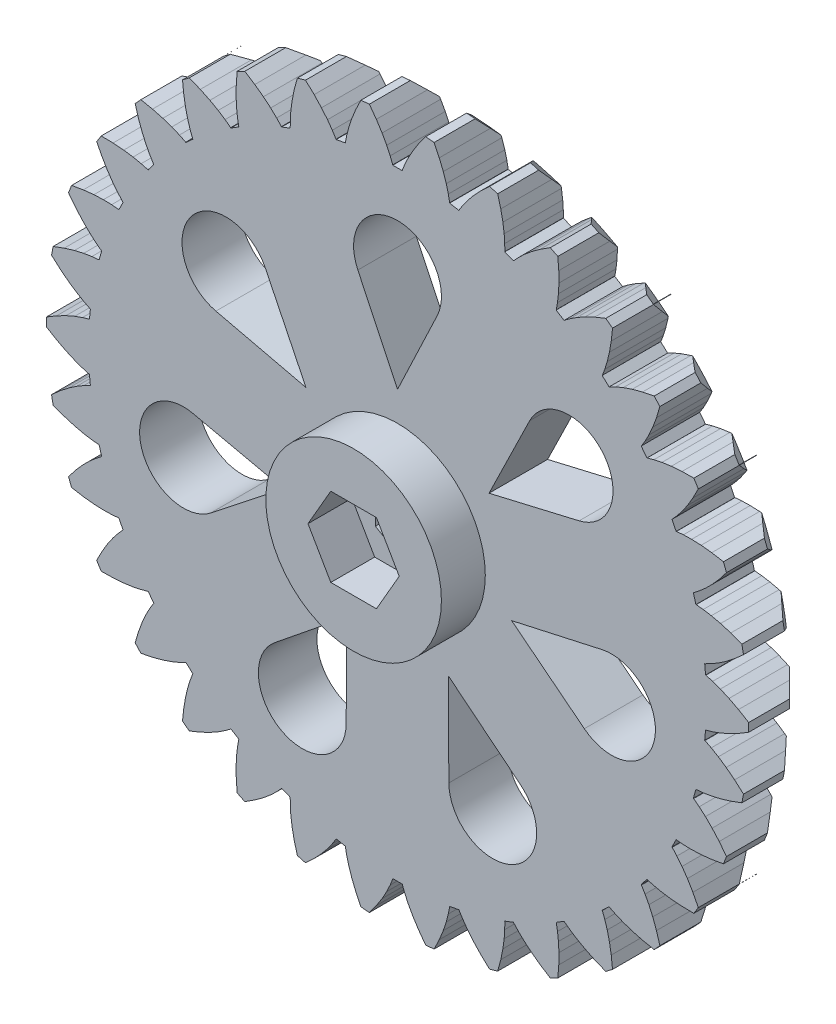
SolidWorks part; units mm, degrees
material "Custom Plastic"
ref_plane "Front Plane" through (0, 0, 0) normal (0, 0, 1) x (1, 0, 0)
ref_plane "Top Plane" through (0, 0, 0) normal (0, 1, 0) x (1, 0, 0)
ref_plane "Right Plane" through (0, 0, 0) normal (1, 0, 0) x (0, 0, -1)
sketch "Model" plane through (0, 0, 0) normal (0, 0, 1) x (1, 0, 0)
  line L0 (-23.998, -0.289) -> (-23.998, 0.289)
  line L1 (-23.998, 0.289) -> (-23.301, 0.707)
  line L2 (-23.301, 0.707) -> (-22.653, 1.042)
  line L3 (-22.653, 1.042) -> (-22.061, 1.301)
  line L4 (-22.061, 1.301) -> (-21.531, 1.492)
  line L5 (-21.531, 1.492) -> (-21.071, 1.627)
  line L6 (-21.071, 1.627) -> (-21.05, 1.625)
  line L7 (-21.05, 1.625) -> (-20.99, 2.27)
  line L8 (-20.99, 2.27) -> (-21.011, 2.272)
  line L9 (-21.011, 2.272) -> (-21.439, 2.49)
  line L10 (-21.439, 2.49) -> (-21.924, 2.775)
  line L11 (-21.924, 2.775) -> (-22.459, 3.138)
  line L12 (-22.459, 3.138) -> (-23.034, 3.587)
  line L13 (-23.034, 3.587) -> (-23.642, 4.126)
  line L14 (-23.642, 4.126) -> (-23.536, 4.694)
  line L15 (-23.536, 4.694) -> (-22.774, 4.977)
  line L16 (-22.774, 4.977) -> (-22.076, 5.187)
  line L17 (-22.076, 5.187) -> (-21.446, 5.333)
  line L18 (-21.446, 5.333) -> (-20.89, 5.423)
  line L19 (-20.89, 5.423) -> (-20.413, 5.471)
  line L20 (-20.413, 5.471) -> (-20.393, 5.466)
  line L21 (-20.393, 5.466) -> (-20.216, 6.089)
  line L22 (-20.216, 6.089) -> (-20.236, 6.095)
  line L23 (-20.236, 6.095) -> (-20.616, 6.387)
  line L24 (-20.616, 6.387) -> (-21.041, 6.756)
  line L25 (-21.041, 6.756) -> (-21.5, 7.212)
  line L26 (-21.5, 7.212) -> (-21.983, 7.758)
  line L27 (-21.983, 7.758) -> (-22.482, 8.4)
  line L28 (-22.482, 8.4) -> (-22.273, 8.939)
  line L29 (-22.273, 8.939) -> (-21.472, 9.077)
  line L30 (-21.472, 9.077) -> (-20.747, 9.155)
  line L31 (-20.747, 9.155) -> (-20.101, 9.182)
  line L32 (-20.101, 9.182) -> (-19.538, 9.169)
  line L33 (-19.538, 9.169) -> (-19.06, 9.129)
  line L34 (-19.06, 9.129) -> (-19.042, 9.12)
  line L35 (-19.042, 9.12) -> (-18.753, 9.7)
  line L36 (-18.753, 9.7) -> (-18.771, 9.709)
  line L37 (-18.771, 9.709) -> (-19.091, 10.066)
  line L38 (-19.091, 10.066) -> (-19.442, 10.507)
  line L39 (-19.442, 10.507) -> (-19.809, 11.039)
  line L40 (-19.809, 11.039) -> (-20.183, 11.665)
  line L41 (-20.183, 11.665) -> (-20.556, 12.388)
  line L42 (-20.556, 12.388) -> (-20.251, 12.879)
  line L43 (-20.251, 12.879) -> (-19.439, 12.867)
  line L44 (-19.439, 12.867) -> (-18.711, 12.811)
  line L45 (-18.711, 12.811) -> (-18.072, 12.72)
  line L46 (-18.072, 12.72) -> (-17.521, 12.603)
  line L47 (-17.521, 12.603) -> (-17.058, 12.476)
  line L48 (-17.058, 12.476) -> (-17.042, 12.464)
  line L49 (-17.042, 12.464) -> (-16.652, 12.98)
  line L50 (-16.652, 12.98) -> (-16.668, 12.993)
  line L51 (-16.668, 12.993) -> (-16.917, 13.403)
  line L52 (-16.917, 13.403) -> (-17.18, 13.901)
  line L53 (-17.18, 13.901) -> (-17.443, 14.491)
  line L54 (-17.443, 14.491) -> (-17.696, 15.175)
  line L55 (-17.696, 15.175) -> (-17.929, 15.954)
  line L56 (-17.929, 15.954) -> (-17.54, 16.381)
  line L57 (-17.54, 16.381) -> (-16.743, 16.22)
  line L58 (-16.743, 16.22) -> (-16.039, 16.031)
  line L59 (-16.039, 16.031) -> (-15.427, 15.824)
  line L60 (-15.427, 15.824) -> (-14.906, 15.608)
  line L61 (-14.906, 15.608) -> (-14.476, 15.398)
  line L62 (-14.476, 15.398) -> (-14.462, 15.383)
  line L63 (-14.462, 15.383) -> (-13.983, 15.82)
  line L64 (-13.983, 15.82) -> (-13.996, 15.835)
  line L65 (-13.996, 15.835) -> (-14.166, 16.283)
  line L66 (-14.166, 16.283) -> (-14.333, 16.821)
  line L67 (-14.333, 16.821) -> (-14.483, 17.45)
  line L68 (-14.483, 17.45) -> (-14.606, 18.169)
  line L69 (-14.606, 18.169) -> (-14.693, 18.977)
  line L70 (-14.693, 18.977) -> (-14.231, 19.325)
  line L71 (-14.231, 19.325) -> (-13.478, 19.021)
  line L72 (-13.478, 19.021) -> (-12.82, 18.705)
  line L73 (-12.82, 18.705) -> (-12.257, 18.389)
  line L74 (-12.257, 18.389) -> (-11.785, 18.081)
  line L75 (-11.785, 18.081) -> (-11.4, 17.796)
  line L76 (-11.4, 17.796) -> (-11.389, 17.779)
  line L77 (-11.389, 17.779) -> (-10.838, 18.119)
  line L78 (-10.838, 18.119) -> (-10.849, 18.137)
  line L79 (-10.849, 18.137) -> (-10.933, 18.609)
  line L80 (-10.933, 18.609) -> (-10.998, 19.168)
  line L81 (-10.998, 19.168) -> (-11.03, 19.814)
  line L82 (-11.03, 19.814) -> (-11.019, 20.543)
  line L83 (-11.019, 20.543) -> (-10.956, 21.353)
  line L84 (-10.956, 21.353) -> (-10.438, 21.611)
  line L85 (-10.438, 21.611) -> (-9.753, 21.173)
  line L86 (-9.753, 21.173) -> (-9.165, 20.743)
  line L87 (-9.165, 20.743) -> (-8.669, 20.328)
  line L88 (-8.669, 20.328) -> (-8.262, 19.939)
  line L89 (-8.262, 19.939) -> (-7.936, 19.587)
  line L90 (-7.936, 19.587) -> (-7.928, 19.568)
  line L91 (-7.928, 19.568) -> (-7.324, 19.802)
  line L92 (-7.324, 19.802) -> (-7.331, 19.821)
  line L93 (-7.331, 19.821) -> (-7.327, 20.301)
  line L94 (-7.327, 20.301) -> (-7.289, 20.863)
  line L95 (-7.289, 20.863) -> (-7.202, 21.503)
  line L96 (-7.202, 21.503) -> (-7.057, 22.218)
  line L97 (-7.057, 22.218) -> (-6.845, 23.003)
  line L98 (-6.845, 23.003) -> (-6.289, 23.161)
  line L99 (-6.289, 23.161) -> (-5.697, 22.605)
  line L100 (-5.697, 22.605) -> (-5.197, 22.073)
  line L101 (-5.197, 22.073) -> (-4.786, 21.575)
  line L102 (-4.786, 21.575) -> (-4.457, 21.117)
  line L103 (-4.457, 21.117) -> (-4.201, 20.712)
  line L104 (-4.201, 20.712) -> (-4.197, 20.692)
  line L105 (-4.197, 20.692) -> (-3.56, 20.81)
  line L106 (-3.56, 20.81) -> (-3.564, 20.831)
  line L107 (-3.564, 20.831) -> (-3.472, 21.301)
  line L108 (-3.472, 21.301) -> (-3.331, 21.847)
  line L109 (-3.331, 21.847) -> (-3.128, 22.46)
  line L110 (-3.128, 22.46) -> (-2.854, 23.136)
  line L111 (-2.854, 23.136) -> (-2.502, 23.869)
  line L112 (-2.502, 23.869) -> (-1.926, 23.922)
  line L113 (-1.926, 23.922) -> (-1.446, 23.267)
  line L114 (-1.446, 23.267) -> (-1.053, 22.653)
  line L115 (-1.053, 22.653) -> (-0.74, 22.087)
  line L116 (-0.74, 22.087) -> (-0.501, 21.577)
  line L117 (-0.501, 21.577) -> (-0.324, 21.131)
  line L118 (-0.324, 21.131) -> (-0.324, 21.111)
  line L119 (-0.324, 21.111) -> (0.324, 21.11)
  line L120 (0.324, 21.11) -> (0.324, 21.131)
  line L121 (0.324, 21.131) -> (0.501, 21.577)
  line L122 (0.501, 21.577) -> (0.74, 22.087)
  line L123 (0.74, 22.087) -> (1.053, 22.653)
  line L124 (1.053, 22.653) -> (1.446, 23.267)
  line L125 (1.446, 23.267) -> (1.926, 23.922)
  line L126 (1.926, 23.922) -> (2.502, 23.869)
  line L127 (2.502, 23.869) -> (2.854, 23.136)
  line L128 (2.854, 23.136) -> (3.128, 22.46)
  line L129 (3.128, 22.46) -> (3.331, 21.847)
  line L130 (3.331, 21.847) -> (3.472, 21.301)
  line L131 (3.472, 21.301) -> (3.564, 20.831)
  line L132 (3.564, 20.831) -> (3.56, 20.81)
  line L133 (3.56, 20.81) -> (4.197, 20.692)
  line L134 (4.197, 20.692) -> (4.201, 20.712)
  line L135 (4.201, 20.712) -> (4.457, 21.117)
  line L136 (4.457, 21.117) -> (4.786, 21.575)
  line L137 (4.786, 21.575) -> (5.197, 22.073)
  line L138 (5.197, 22.073) -> (5.697, 22.605)
  line L139 (5.697, 22.605) -> (6.289, 23.161)
  line L140 (6.289, 23.161) -> (6.845, 23.003)
  line L141 (6.845, 23.003) -> (7.057, 22.218)
  line L142 (7.057, 22.218) -> (7.202, 21.503)
  line L143 (7.202, 21.503) -> (7.289, 20.863)
  line L144 (7.289, 20.863) -> (7.327, 20.301)
  line L145 (7.327, 20.301) -> (7.331, 19.821)
  line L146 (7.331, 19.821) -> (7.324, 19.802)
  line L147 (7.324, 19.802) -> (7.928, 19.568)
  line L148 (7.928, 19.568) -> (7.936, 19.587)
  line L149 (7.936, 19.587) -> (8.262, 19.939)
  line L150 (8.262, 19.939) -> (8.669, 20.328)
  line L151 (8.669, 20.328) -> (9.165, 20.743)
  line L152 (9.165, 20.743) -> (9.753, 21.173)
  line L153 (9.753, 21.173) -> (10.438, 21.611)
  line L154 (10.438, 21.611) -> (10.956, 21.353)
  line L155 (10.956, 21.353) -> (11.019, 20.543)
  line L156 (11.019, 20.543) -> (11.03, 19.814)
  line L157 (11.03, 19.814) -> (10.998, 19.168)
  line L158 (10.998, 19.168) -> (10.933, 18.609)
  line L159 (10.933, 18.609) -> (10.849, 18.137)
  line L160 (10.849, 18.137) -> (10.838, 18.119)
  line L161 (10.838, 18.119) -> (11.389, 17.778)
  line L162 (11.389, 17.778) -> (11.4, 17.796)
  line L163 (11.4, 17.796) -> (11.785, 18.081)
  line L164 (11.785, 18.081) -> (12.257, 18.389)
  line L165 (12.257, 18.389) -> (12.82, 18.705)
  line L166 (12.82, 18.705) -> (13.478, 19.021)
  line L167 (13.478, 19.021) -> (14.231, 19.325)
  line L168 (14.231, 19.325) -> (14.693, 18.977)
  line L169 (14.693, 18.977) -> (14.606, 18.169)
  line L170 (14.606, 18.169) -> (14.483, 17.45)
  line L171 (14.483, 17.45) -> (14.333, 16.821)
  line L172 (14.333, 16.821) -> (14.166, 16.283)
  line L173 (14.166, 16.283) -> (13.996, 15.835)
  line L174 (13.996, 15.835) -> (13.983, 15.82)
  line L175 (13.983, 15.82) -> (14.462, 15.383)
  line L176 (14.462, 15.383) -> (14.476, 15.398)
  line L177 (14.476, 15.398) -> (14.906, 15.608)
  line L178 (14.906, 15.608) -> (15.427, 15.824)
  line L179 (15.427, 15.824) -> (16.039, 16.031)
  line L180 (16.039, 16.031) -> (16.743, 16.22)
  line L181 (16.743, 16.22) -> (17.54, 16.381)
  line L182 (17.54, 16.381) -> (17.929, 15.954)
  line L183 (17.929, 15.954) -> (17.696, 15.175)
  line L184 (17.696, 15.175) -> (17.443, 14.491)
  line L185 (17.443, 14.491) -> (17.18, 13.901)
  line L186 (17.18, 13.901) -> (16.917, 13.403)
  line L187 (16.917, 13.403) -> (16.668, 12.993)
  line L188 (16.668, 12.993) -> (16.652, 12.981)
  line L189 (16.652, 12.981) -> (17.042, 12.464)
  line L190 (17.042, 12.464) -> (17.058, 12.476)
  line L191 (17.058, 12.476) -> (17.521, 12.603)
  line L192 (17.521, 12.603) -> (18.072, 12.72)
  line L193 (18.072, 12.72) -> (18.711, 12.811)
  line L194 (18.711, 12.811) -> (19.439, 12.867)
  line L195 (19.439, 12.867) -> (20.251, 12.879)
  line L196 (20.251, 12.879) -> (20.556, 12.388)
  line L197 (20.556, 12.388) -> (20.183, 11.665)
  line L198 (20.183, 11.665) -> (19.809, 11.039)
  line L199 (19.809, 11.039) -> (19.442, 10.507)
  line L200 (19.442, 10.507) -> (19.091, 10.066)
  line L201 (19.091, 10.066) -> (18.771, 9.709)
  line L202 (18.771, 9.709) -> (18.753, 9.7)
  line L203 (18.753, 9.7) -> (19.042, 9.12)
  line L204 (19.042, 9.12) -> (19.06, 9.129)
  line L205 (19.06, 9.129) -> (19.538, 9.169)
  line L206 (19.538, 9.169) -> (20.101, 9.182)
  line L207 (20.101, 9.182) -> (20.747, 9.155)
  line L208 (20.747, 9.155) -> (21.472, 9.077)
  line L209 (21.472, 9.077) -> (22.273, 8.939)
  line L210 (22.273, 8.939) -> (22.482, 8.4)
  line L211 (22.482, 8.4) -> (21.983, 7.758)
  line L212 (21.983, 7.758) -> (21.5, 7.212)
  line L213 (21.5, 7.212) -> (21.041, 6.756)
  line L214 (21.041, 6.756) -> (20.616, 6.387)
  line L215 (20.616, 6.387) -> (20.236, 6.095)
  line L216 (20.236, 6.095) -> (20.216, 6.089)
  line L217 (20.216, 6.089) -> (20.393, 5.466)
  line L218 (20.393, 5.466) -> (20.413, 5.471)
  line L219 (20.413, 5.471) -> (20.89, 5.423)
  line L220 (20.89, 5.423) -> (21.446, 5.333)
  line L221 (21.446, 5.333) -> (22.076, 5.187)
  line L222 (22.076, 5.187) -> (22.774, 4.977)
  line L223 (22.774, 4.977) -> (23.536, 4.694)
  line L224 (23.536, 4.694) -> (23.642, 4.126)
  line L225 (23.642, 4.126) -> (23.034, 3.587)
  line L226 (23.034, 3.587) -> (22.459, 3.138)
  line L227 (22.459, 3.138) -> (21.924, 2.775)
  line L228 (21.924, 2.775) -> (21.439, 2.49)
  line L229 (21.439, 2.49) -> (21.011, 2.272)
  line L230 (21.011, 2.272) -> (20.99, 2.27)
  line L231 (20.99, 2.27) -> (21.051, 1.625)
  line L232 (21.051, 1.625) -> (21.071, 1.627)
  line L233 (21.071, 1.627) -> (21.531, 1.492)
  line L234 (21.531, 1.492) -> (22.061, 1.301)
  line L235 (22.061, 1.301) -> (22.653, 1.042)
  line L236 (22.653, 1.042) -> (23.301, 0.707)
  line L237 (23.301, 0.707) -> (23.998, 0.289)
  line L238 (23.998, 0.289) -> (23.998, -0.289)
  line L239 (23.998, -0.289) -> (23.301, -0.707)
  line L240 (23.301, -0.707) -> (22.653, -1.042)
  line L241 (22.653, -1.042) -> (22.061, -1.301)
  line L242 (22.061, -1.301) -> (21.531, -1.492)
  line L243 (21.531, -1.492) -> (21.071, -1.627)
  line L244 (21.071, -1.627) -> (21.05, -1.625)
  line L245 (21.05, -1.625) -> (20.99, -2.27)
  line L246 (20.99, -2.27) -> (21.011, -2.272)
  line L247 (21.011, -2.272) -> (21.439, -2.49)
  line L248 (21.439, -2.49) -> (21.924, -2.775)
  line L249 (21.924, -2.775) -> (22.459, -3.138)
  line L250 (22.459, -3.138) -> (23.034, -3.587)
  line L251 (23.034, -3.587) -> (23.642, -4.126)
  line L252 (23.642, -4.126) -> (23.536, -4.694)
  line L253 (23.536, -4.694) -> (22.774, -4.977)
  line L254 (22.774, -4.977) -> (22.076, -5.187)
  line L255 (22.076, -5.187) -> (21.446, -5.333)
  line L256 (21.446, -5.333) -> (20.89, -5.423)
  line L257 (20.89, -5.423) -> (20.413, -5.471)
  line L258 (20.413, -5.471) -> (20.393, -5.466)
  line L259 (20.393, -5.466) -> (20.216, -6.089)
  line L260 (20.216, -6.089) -> (20.236, -6.095)
  line L261 (20.236, -6.095) -> (20.616, -6.387)
  line L262 (20.616, -6.387) -> (21.041, -6.756)
  line L263 (21.041, -6.756) -> (21.5, -7.212)
  line L264 (21.5, -7.212) -> (21.983, -7.758)
  line L265 (21.983, -7.758) -> (22.482, -8.4)
  line L266 (22.482, -8.4) -> (22.273, -8.939)
  line L267 (22.273, -8.939) -> (21.472, -9.077)
  line L268 (21.472, -9.077) -> (20.747, -9.155)
  line L269 (20.747, -9.155) -> (20.101, -9.182)
  line L270 (20.101, -9.182) -> (19.538, -9.169)
  line L271 (19.538, -9.169) -> (19.06, -9.129)
  line L272 (19.06, -9.129) -> (19.042, -9.12)
  line L273 (19.042, -9.12) -> (18.753, -9.7)
  line L274 (18.753, -9.7) -> (18.771, -9.709)
  line L275 (18.771, -9.709) -> (19.091, -10.066)
  line L276 (19.091, -10.066) -> (19.442, -10.507)
  line L277 (19.442, -10.507) -> (19.809, -11.039)
  line L278 (19.809, -11.039) -> (20.183, -11.665)
  line L279 (20.183, -11.665) -> (20.556, -12.388)
  line L280 (20.556, -12.388) -> (20.251, -12.879)
  line L281 (20.251, -12.879) -> (19.439, -12.867)
  line L282 (19.439, -12.867) -> (18.711, -12.811)
  line L283 (18.711, -12.811) -> (18.072, -12.72)
  line L284 (18.072, -12.72) -> (17.521, -12.603)
  line L285 (17.521, -12.603) -> (17.058, -12.476)
  line L286 (17.058, -12.476) -> (17.042, -12.464)
  line L287 (17.042, -12.464) -> (16.652, -12.98)
  line L288 (16.652, -12.98) -> (16.668, -12.993)
  line L289 (16.668, -12.993) -> (16.917, -13.403)
  line L290 (16.917, -13.403) -> (17.18, -13.901)
  line L291 (17.18, -13.901) -> (17.443, -14.491)
  line L292 (17.443, -14.491) -> (17.696, -15.175)
  line L293 (17.696, -15.175) -> (17.929, -15.954)
  line L294 (17.929, -15.954) -> (17.54, -16.381)
  line L295 (17.54, -16.381) -> (16.743, -16.22)
  line L296 (16.743, -16.22) -> (16.039, -16.031)
  line L297 (16.039, -16.031) -> (15.427, -15.824)
  line L298 (15.427, -15.824) -> (14.906, -15.608)
  line L299 (14.906, -15.608) -> (14.476, -15.398)
  line L300 (14.476, -15.398) -> (14.462, -15.383)
  line L301 (14.462, -15.383) -> (13.983, -15.82)
  line L302 (13.983, -15.82) -> (13.996, -15.835)
  line L303 (13.996, -15.835) -> (14.166, -16.283)
  line L304 (14.166, -16.283) -> (14.333, -16.821)
  line L305 (14.333, -16.821) -> (14.483, -17.45)
  line L306 (14.483, -17.45) -> (14.606, -18.169)
  line L307 (14.606, -18.169) -> (14.693, -18.977)
  line L308 (14.693, -18.977) -> (14.231, -19.325)
  line L309 (14.231, -19.325) -> (13.478, -19.021)
  line L310 (13.478, -19.021) -> (12.82, -18.705)
  line L311 (12.82, -18.705) -> (12.257, -18.389)
  line L312 (12.257, -18.389) -> (11.785, -18.081)
  line L313 (11.785, -18.081) -> (11.4, -17.796)
  line L314 (11.4, -17.796) -> (11.389, -17.779)
  line L315 (11.389, -17.779) -> (10.838, -18.119)
  line L316 (10.838, -18.119) -> (10.849, -18.137)
  line L317 (10.849, -18.137) -> (10.933, -18.609)
  line L318 (10.933, -18.609) -> (10.998, -19.168)
  line L319 (10.998, -19.168) -> (11.03, -19.814)
  line L320 (11.03, -19.814) -> (11.019, -20.543)
  line L321 (11.019, -20.543) -> (10.956, -21.353)
  line L322 (10.956, -21.353) -> (10.438, -21.611)
  line L323 (10.438, -21.611) -> (9.753, -21.173)
  line L324 (9.753, -21.173) -> (9.165, -20.743)
  line L325 (9.165, -20.743) -> (8.669, -20.328)
  line L326 (8.669, -20.328) -> (8.262, -19.939)
  line L327 (8.262, -19.939) -> (7.936, -19.587)
  line L328 (7.936, -19.587) -> (7.928, -19.568)
  line L329 (7.928, -19.568) -> (7.324, -19.802)
  line L330 (7.324, -19.802) -> (7.331, -19.821)
  line L331 (7.331, -19.821) -> (7.327, -20.301)
  line L332 (7.327, -20.301) -> (7.289, -20.863)
  line L333 (7.289, -20.863) -> (7.202, -21.503)
  line L334 (7.202, -21.503) -> (7.057, -22.218)
  line L335 (7.057, -22.218) -> (6.845, -23.003)
  line L336 (6.845, -23.003) -> (6.289, -23.161)
  line L337 (6.289, -23.161) -> (5.697, -22.605)
  line L338 (5.697, -22.605) -> (5.197, -22.073)
  line L339 (5.197, -22.073) -> (4.786, -21.575)
  line L340 (4.786, -21.575) -> (4.457, -21.117)
  line L341 (4.457, -21.117) -> (4.201, -20.712)
  line L342 (4.201, -20.712) -> (4.197, -20.692)
  line L343 (4.197, -20.692) -> (3.56, -20.81)
  line L344 (3.56, -20.81) -> (3.564, -20.831)
  line L345 (3.564, -20.831) -> (3.472, -21.301)
  line L346 (3.472, -21.301) -> (3.331, -21.847)
  line L347 (3.331, -21.847) -> (3.128, -22.46)
  line L348 (3.128, -22.46) -> (2.854, -23.136)
  line L349 (2.854, -23.136) -> (2.502, -23.869)
  line L350 (2.502, -23.869) -> (1.926, -23.922)
  line L351 (1.926, -23.922) -> (1.446, -23.267)
  line L352 (1.446, -23.267) -> (1.053, -22.653)
  line L353 (1.053, -22.653) -> (0.74, -22.087)
  line L354 (0.74, -22.087) -> (0.501, -21.577)
  line L355 (0.501, -21.577) -> (0.324, -21.131)
  line L356 (0.324, -21.131) -> (0.324, -21.111)
  line L357 (0.324, -21.111) -> (-0.324, -21.11)
  line L358 (-0.324, -21.11) -> (-0.324, -21.131)
  line L359 (-0.324, -21.131) -> (-0.501, -21.577)
  line L360 (-0.501, -21.577) -> (-0.74, -22.087)
  line L361 (-0.74, -22.087) -> (-1.053, -22.653)
  line L362 (-1.053, -22.653) -> (-1.446, -23.267)
  line L363 (-1.446, -23.267) -> (-1.926, -23.922)
  line L364 (-1.926, -23.922) -> (-2.502, -23.869)
  line L365 (-2.502, -23.869) -> (-2.854, -23.136)
  line L366 (-2.854, -23.136) -> (-3.128, -22.46)
  line L367 (-3.128, -22.46) -> (-3.331, -21.847)
  line L368 (-3.331, -21.847) -> (-3.472, -21.301)
  line L369 (-3.472, -21.301) -> (-3.564, -20.831)
  line L370 (-3.564, -20.831) -> (-3.56, -20.81)
  line L371 (-3.56, -20.81) -> (-4.197, -20.692)
  line L372 (-4.197, -20.692) -> (-4.201, -20.712)
  line L373 (-4.201, -20.712) -> (-4.457, -21.117)
  line L374 (-4.457, -21.117) -> (-4.786, -21.575)
  line L375 (-4.786, -21.575) -> (-5.197, -22.073)
  line L376 (-5.197, -22.073) -> (-5.697, -22.605)
  line L377 (-5.697, -22.605) -> (-6.289, -23.161)
  line L378 (-6.289, -23.161) -> (-6.845, -23.003)
  line L379 (-6.845, -23.003) -> (-7.057, -22.218)
  line L380 (-7.057, -22.218) -> (-7.202, -21.503)
  line L381 (-7.202, -21.503) -> (-7.289, -20.863)
  line L382 (-7.289, -20.863) -> (-7.327, -20.301)
  line L383 (-7.327, -20.301) -> (-7.331, -19.821)
  line L384 (-7.331, -19.821) -> (-7.324, -19.802)
  line L385 (-7.324, -19.802) -> (-7.928, -19.568)
  line L386 (-7.928, -19.568) -> (-7.936, -19.587)
  line L387 (-7.936, -19.587) -> (-8.262, -19.939)
  line L388 (-8.262, -19.939) -> (-8.669, -20.328)
  line L389 (-8.669, -20.328) -> (-9.165, -20.743)
  line L390 (-9.165, -20.743) -> (-9.753, -21.173)
  line L391 (-9.753, -21.173) -> (-10.438, -21.611)
  line L392 (-10.438, -21.611) -> (-10.956, -21.353)
  line L393 (-10.956, -21.353) -> (-11.019, -20.543)
  line L394 (-11.019, -20.543) -> (-11.03, -19.814)
  line L395 (-11.03, -19.814) -> (-10.998, -19.168)
  line L396 (-10.998, -19.168) -> (-10.933, -18.609)
  line L397 (-10.933, -18.609) -> (-10.849, -18.137)
  line L398 (-10.849, -18.137) -> (-10.838, -18.119)
  line L399 (-10.838, -18.119) -> (-11.389, -17.778)
  line L400 (-11.389, -17.778) -> (-11.4, -17.796)
  line L401 (-11.4, -17.796) -> (-11.785, -18.081)
  line L402 (-11.785, -18.081) -> (-12.257, -18.389)
  line L403 (-12.257, -18.389) -> (-12.82, -18.705)
  line L404 (-12.82, -18.705) -> (-13.478, -19.021)
  line L405 (-13.478, -19.021) -> (-14.231, -19.325)
  line L406 (-14.231, -19.325) -> (-14.693, -18.977)
  line L407 (-14.693, -18.977) -> (-14.606, -18.169)
  line L408 (-14.606, -18.169) -> (-14.483, -17.45)
  line L409 (-14.483, -17.45) -> (-14.333, -16.821)
  line L410 (-14.333, -16.821) -> (-14.166, -16.283)
  line L411 (-14.166, -16.283) -> (-13.996, -15.835)
  line L412 (-13.996, -15.835) -> (-13.983, -15.82)
  line L413 (-13.983, -15.82) -> (-14.462, -15.383)
  line L414 (-14.462, -15.383) -> (-14.476, -15.398)
  line L415 (-14.476, -15.398) -> (-14.906, -15.608)
  line L416 (-14.906, -15.608) -> (-15.427, -15.824)
  line L417 (-15.427, -15.824) -> (-16.039, -16.031)
  line L418 (-16.039, -16.031) -> (-16.743, -16.22)
  line L419 (-16.743, -16.22) -> (-17.54, -16.381)
  line L420 (-17.54, -16.381) -> (-17.929, -15.954)
  line L421 (-17.929, -15.954) -> (-17.696, -15.175)
  line L422 (-17.696, -15.175) -> (-17.443, -14.491)
  line L423 (-17.443, -14.491) -> (-17.18, -13.901)
  line L424 (-17.18, -13.901) -> (-16.917, -13.403)
  line L425 (-16.917, -13.403) -> (-16.668, -12.993)
  line L426 (-16.668, -12.993) -> (-16.652, -12.981)
  line L427 (-16.652, -12.981) -> (-17.042, -12.464)
  line L428 (-17.042, -12.464) -> (-17.058, -12.476)
  line L429 (-17.058, -12.476) -> (-17.521, -12.603)
  line L430 (-17.521, -12.603) -> (-18.072, -12.72)
  line L431 (-18.072, -12.72) -> (-18.711, -12.811)
  line L432 (-18.711, -12.811) -> (-19.439, -12.867)
  line L433 (-19.439, -12.867) -> (-20.251, -12.879)
  line L434 (-20.251, -12.879) -> (-20.556, -12.388)
  line L435 (-20.556, -12.388) -> (-20.183, -11.665)
  line L436 (-20.183, -11.665) -> (-19.809, -11.039)
  line L437 (-19.809, -11.039) -> (-19.442, -10.507)
  line L438 (-19.442, -10.507) -> (-19.091, -10.066)
  line L439 (-19.091, -10.066) -> (-18.771, -9.709)
  line L440 (-18.771, -9.709) -> (-18.753, -9.7)
  line L441 (-18.753, -9.7) -> (-19.042, -9.12)
  line L442 (-19.042, -9.12) -> (-19.06, -9.129)
  line L443 (-19.06, -9.129) -> (-19.538, -9.169)
  line L444 (-19.538, -9.169) -> (-20.101, -9.182)
  line L445 (-20.101, -9.182) -> (-20.747, -9.155)
  line L446 (-20.747, -9.155) -> (-21.472, -9.077)
  line L447 (-21.472, -9.077) -> (-22.273, -8.939)
  line L448 (-22.273, -8.939) -> (-22.482, -8.4)
  line L449 (-22.482, -8.4) -> (-21.983, -7.758)
  line L450 (-21.983, -7.758) -> (-21.5, -7.212)
  line L451 (-21.5, -7.212) -> (-21.041, -6.756)
  line L452 (-21.041, -6.756) -> (-20.616, -6.387)
  line L453 (-20.616, -6.387) -> (-20.236, -6.095)
  line L454 (-20.236, -6.095) -> (-20.216, -6.089)
  line L455 (-20.216, -6.089) -> (-20.393, -5.466)
  line L456 (-20.393, -5.466) -> (-20.413, -5.471)
  line L457 (-20.413, -5.471) -> (-20.89, -5.423)
  line L458 (-20.89, -5.423) -> (-21.446, -5.333)
  line L459 (-21.446, -5.333) -> (-22.076, -5.187)
  line L460 (-22.076, -5.187) -> (-22.774, -4.977)
  line L461 (-22.774, -4.977) -> (-23.536, -4.694)
  line L462 (-23.536, -4.694) -> (-23.642, -4.126)
  line L463 (-23.642, -4.126) -> (-23.034, -3.587)
  line L464 (-23.034, -3.587) -> (-22.459, -3.138)
  line L465 (-22.459, -3.138) -> (-21.924, -2.775)
  line L466 (-21.924, -2.775) -> (-21.439, -2.49)
  line L467 (-21.439, -2.49) -> (-21.011, -2.272)
  line L468 (-21.011, -2.272) -> (-20.99, -2.27)
  line L469 (-20.99, -2.27) -> (-21.051, -1.625)
  line L470 (-21.051, -1.625) -> (-21.071, -1.627)
  line L471 (-21.071, -1.627) -> (-21.531, -1.492)
  line L472 (-21.531, -1.492) -> (-22.061, -1.301)
  line L473 (-22.061, -1.301) -> (-22.653, -1.042)
  line L474 (-22.653, -1.042) -> (-23.301, -0.707)
  line L475 (-23.301, -0.707) -> (-23.998, -0.289)
extrude "Boss-Extrude1" add sketch "Model" along normal blind 4
sketch "Sketch3" plane through (0, 0, 4) normal (0, 0, 1) x (1, 0, 0)
  circle A0 centre (0, 0) radius 6
  dimension "D1" = 12
extrude "Boss-Extrude2" add sketch "Sketch3" along normal blind 3
sketch "Sketch2" plane through (0, 0, 7) normal (0, 0, 1) x (1, 0, 0)
  line L1 (1.4916, -0.8805) -> (1.5083, 0.8515)
  line L2 (1.5083, 0.8515) -> (0.0167, 1.732)
  line L3 (0.0167, 1.732) -> (-1.4916, 0.8805)
  line L4 (-1.4916, 0.8805) -> (-1.5083, -0.8515)
  line L5 (-1.5083, -0.8515) -> (-0.0167, -1.732)
  line L6 (-0.0167, -1.732) -> (1.4916, -0.8805)
  circle A0 centre (0, 0) radius 1.5 construction
  dimension "D1" = 3
extrude "Cut-Extrude1" cut sketch "Sketch2" against normal through all
sketch "Sketch4" plane through (0, 0, 7) normal (0, 0, 1) x (1, 0, 0)
  line L1 (3.1177, 0) -> (1.5588, 2.7)
  line L2 (1.5588, 2.7) -> (-1.5588, 2.7)
  line L3 (-1.5588, 2.7) -> (-3.1177, 0)
  line L4 (-3.1177, 0) -> (-1.5588, -2.7)
  line L5 (-1.5588, -2.7) -> (1.5588, -2.7)
  line L6 (1.5588, -2.7) -> (3.1177, 0)
  circle A0 centre (0, 0) radius 2.7 construction
  dimension "D1" = 5.4
extrude "Cut-Extrude2" cut sketch "Sketch4" against normal blind 3
sketch "Sketch5" plane through (0, 0, 4) normal (0, 0, 1) x (1, 0, 0)
  line L0 (0, 0) -> (0, 15) construction
  line L1 (-2.7105, 13.7143) -> (0, 8)
  line L2 (0, 8) -> (2.7105, 13.7143)
  arc A0 (2.7105, 13.7143) -> (-2.7105, 13.7143) centre (0, 15) ccw
  circle A1 centre (0, 0) radius 6 construction
  dimension "D3" = 3
  dimension "D1" = 8
  dimension "D2" = 15
extrude "Cut-Extrude3" cut sketch "Sketch5" against normal through all
ref_axis "Axis1" through (0, 0, 7.35) along (0, 0, -1)
pattern_circular "CirPattern1" count 7 over 360 about axis through (0, 0, 7.35) along (0, 0, -1) of "Cut-Extrude3"
sketch "Sketch6" plane through (0, 0, 0) normal (0, 1, 0) x (1, 0, 0)
  line L0 (24, 0) -> (22.8, 0)
  line L1 (22.8, 0) -> (24, -1.2)
  line L2 (24, -1.2) -> (24, 0)
  line L4 (0, -7.35) -> (0, 0.35) construction
  dimension "D1" = 45
  dimension "D2" = 1.2
  dimension "D3" = 24
revolve "Cut-Revolve1" cut sketch "Sketch6" angle 360 about axis through (0, 0, 7.35) along (0, 0, -1)
